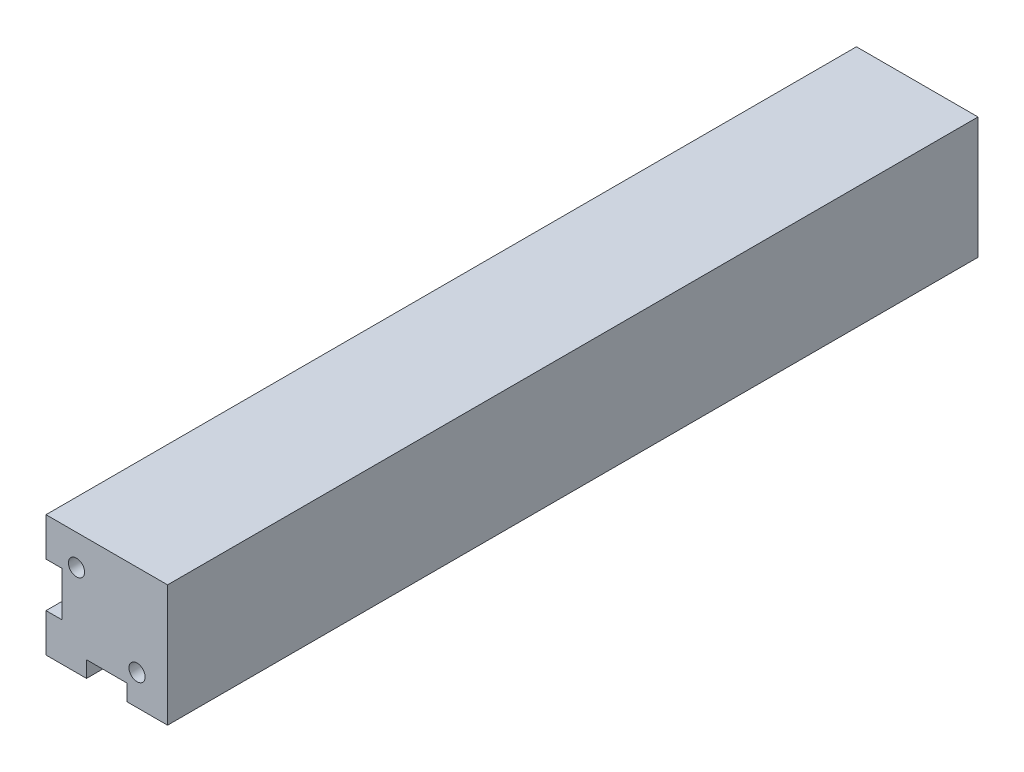
SolidWorks part; units mm, degrees
ref_plane "Alzado" through (0, 0, 0) normal (0, 0, 1) x (1, 0, 0)
ref_plane "Planta" through (0, 0, 0) normal (0, 1, 0) x (1, 0, 0)
ref_plane "Vista lateral" through (0, 0, 0) normal (1, 0, 0) x (0, 0, -1)
sketch "Croquis1" plane through (0, 0, 0) normal (0, 0, 1) x (1, 0, 0)
  line L1 (-15, -15) -> (15, -15)
  line L2 (-15, -15) -> (-15, 15)
  line L3 (-15, 15) -> (15, 15)
  line L4 (15, -15) -> (15, 15)
  line L5 (-15, -15) -> (15, 15) construction
  line L6 (-15, 15) -> (15, -15) construction
  point P0 (0, 0)
  dimension "D1" = 30
extrude "Saliente-Extruir1" add sketch "Croquis1" along normal blind 200
sketch "Croquis2" plane through (0, 0, 200) normal (0, 0, 1) x (1, 0, 0)
  line L0 (-15, 15) -> (15, -15) construction
  line L1 (-15, -15) -> (15, 15) construction
  circle A1 centre (-7.4706, 7.4706) radius 2
  circle A2 centre (7.4706, -7.4706) radius 2
  dimension "D1" = 10.565
extrude "Cortar-Extruir1" cut sketch "Croquis2" against normal blind 25
sketch "Croquis4" plane through (0, 0, 0) normal (0, 0, -1) x (-1, 0, 0)
  circle A0 centre (0, 0) radius 2
extrude "Cortar-Extruir3" cut sketch "Croquis4" against normal blind 25
sketch "Croquis5" plane through (0, 0, 0) normal (0, 0, -1) x (-1, 0, 0)
  line L0 (0, 0) -> (0, -15) construction
  line L1 (15, -15) -> (-15, -15) construction
  line L2 (0, 0) -> (15, 0) construction
  line L3 (-5, -19) -> (5, -19)
  line L4 (-5, -19) -> (-5, -11)
  line L5 (-5, -11) -> (5, -11)
  line L6 (5, -19) -> (5, -11)
  line L7 (-5, -19) -> (5, -11) construction
  line L8 (-5, -11) -> (5, -19) construction
  line L9 (15, 15) -> (15, -15) construction
  line L11 (11, -5.5) -> (19, -5.5)
  line L12 (11, -5.5) -> (11, 5.5)
  line L13 (11, 5.5) -> (19, 5.5)
  line L14 (19, -5.5) -> (19, 5.5)
  line L15 (11, -5.5) -> (19, 5.5) construction
  line L16 (11, 5.5) -> (19, -5.5) construction
  dimension "D1" = 10
  dimension "D2" = 8
  dimension "D3" = 8
  dimension "D4" = 11
extrude "Cortar-Extruir4" cut sketch "Croquis5" against normal blind 200
